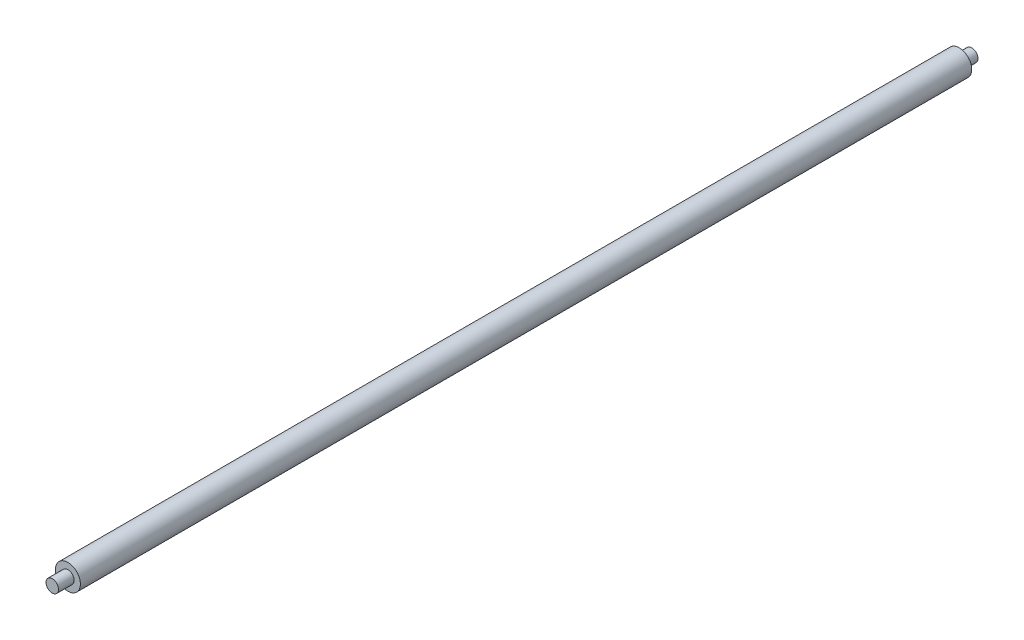
SolidWorks part; units mm, degrees
ref_plane "Front Plane" through (0, 0, 0) normal (0, 0, 1) x (1, 0, 0)
ref_plane "Top Plane" through (0, 0, 0) normal (0, 1, 0) x (1, 0, 0)
ref_plane "Right Plane" through (0, 0, 0) normal (1, 0, 0) x (0, 0, -1)
sketch "Sketch1" plane through (0, 0, 0) normal (0, 0, 1) x (1, 0, 0)
  circle A0 centre (0, 0) radius 6
  dimension "D1" = 12
extrude "Boss-Extrude1" add sketch "Sketch1" along normal mid plane 441
sketch "Sketch2" plane through (0, 0, 220.5) normal (0, 0, 1) x (1, 0, 0)
  circle A0 centre (0, 0) radius 6
  circle A1 centre (0, 0) radius 3
  dimension "D1" = 12
  dimension "D2" = 6
extrude "Cut-Extrude1" cut sketch "Sketch2" against normal blind 7.5
sketch "Sketch3" plane through (0, 0, -220.5) normal (0, 0, -1) x (-1, 0, 0)
  circle A0 centre (0, 0) radius 6
  circle A1 centre (0, 0) radius 3
  dimension "D1" = 6
  dimension "D2" = 12
extrude "Cut-Extrude2" cut sketch "Sketch3" against normal blind 6
